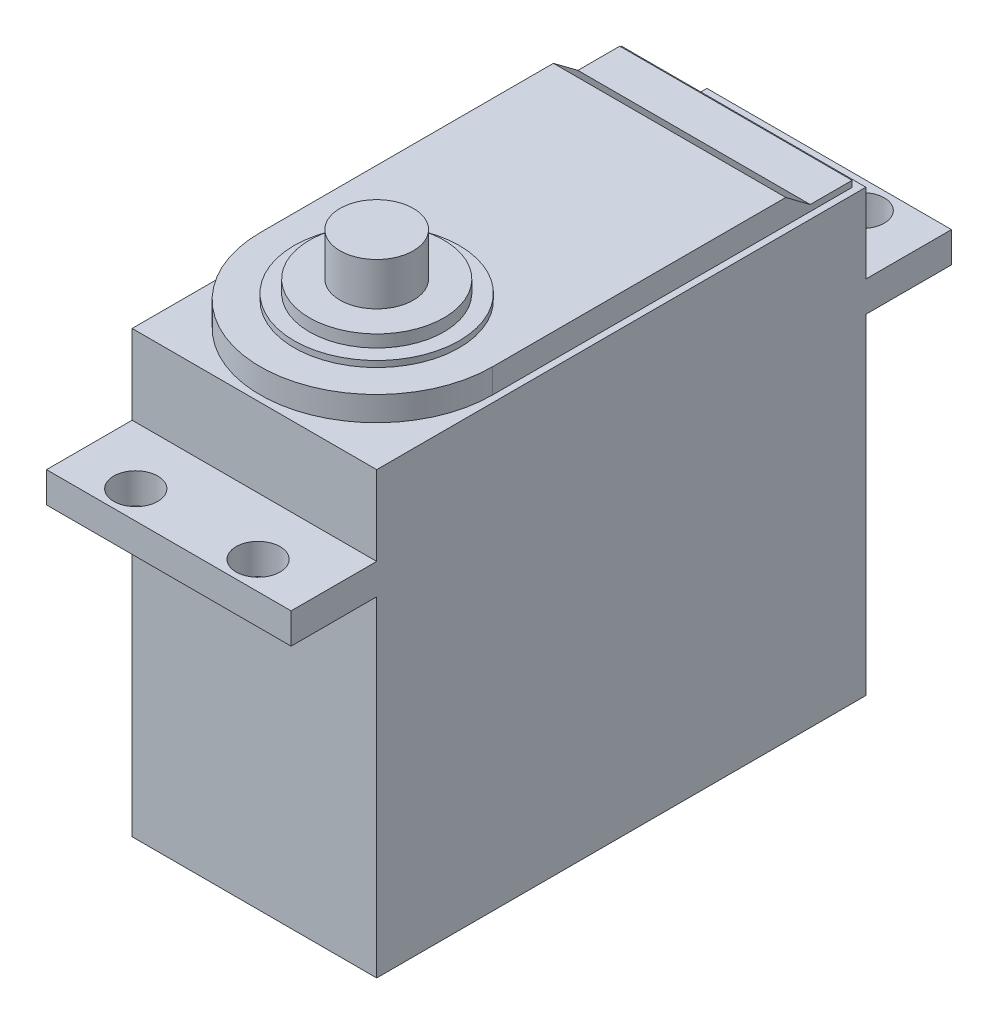
SolidWorks part; units mm, degrees
ref_plane "Front Plane" through (0, 0, 0) normal (0, 0, 1) x (1, 0, 0)
ref_plane "Top Plane" through (0, 0, 0) normal (0, 1, 0) x (1, 0, 0)
ref_plane "Right Plane" through (0, 0, 0) normal (1, 0, 0) x (0, 0, -1)
sketch "Sketch1" plane through (0, 0, 0) normal (0, 0, 1) x (1, 0, 0)
  line L1 (0, 0) -> (20, 0)
  line L2 (0, 0) -> (0, 38)
  line L3 (0, 38) -> (20, 38)
  line L4 (20, 0) -> (20, 38)
  dimension "D1" = 20
  dimension "D2" = 38
extrude "Boss-Extrude1" add sketch "Sketch1" along normal blind 40
sketch "Sketch2" plane through (0, 0, 0) normal (-1, 0, 0) x (0, 0, 1)
  line L0 (0, 0) -> (0, 38) construction
  line L1 (0, 29.5) -> (-7, 29.5)
  line L2 (0, 29.5) -> (0, 27)
  line L3 (0, 27) -> (-7, 27)
  line L4 (-7, 29.5) -> (-7, 27)
  line L5 (40, 0) -> (0, 0) construction
  line L6 (40, 0) -> (40, 38) construction
  line L7 (40, 29.5) -> (47, 29.5)
  line L8 (40, 29.5) -> (40, 27)
  line L9 (40, 27) -> (47, 27)
  line L10 (47, 29.5) -> (47, 27)
  dimension "D1" = 29.5
  dimension "D2" = 2.5
  dimension "D3" = 7
  dimension "D4" = 7
  dimension "D5" = 29.5
  dimension "D6" = 2.5
extrude "Boss-Extrude2" add sketch "Sketch2" against normal up to surface (20 mm away) up to face at (20, 19, 20)
sketch "Sketch3" plane through (0, 0, 0) normal (-1, 0, 0) x (0, 0, 1)
  line L0 (6, 38) -> (4, 36.5)
  line L1 (40, 38) -> (0, 38) construction
  line L2 (4, 36.5) -> (0, 36.5)
  line L3 (0, 29.5) -> (0, 38) construction
  line L4 (6, 38) -> (0, 38)
  line L5 (0, 38) -> (0, 36.5)
  dimension "D1" = 1.5
  dimension "D2" = 4
  dimension "D3" = 6
extrude "Cut-Extrude1" cut sketch "Sketch3" against normal blind 40
sketch "Sketch4" plane through (0, 29.5, 0) normal (0, 1, 0) x (1, 0, 0)
  line L0 (20, -40) -> (0, -40) construction
  line L1 (0, -47) -> (0, -40) construction
  line L2 (0, 0) -> (0, 7) construction
  line L3 (20, 0) -> (0, 0) construction
  circle A0 centre (15, -44.7) radius 1.8
  circle A1 centre (5, -44.7) radius 1.8
  circle A3 centre (15, 4.7) radius 1.8
  circle A4 centre (5, 4.7) radius 1.8
  dimension "D1" = 3.6
  dimension "D2" = 10
  dimension "D3" = 4.7
  dimension "D4" = 4.7
  dimension "D5" = 5
  dimension "D6" = 10
  dimension "D7" = 5
  dimension "D8" = 4.7
extrude "Cut-Extrude2" cut sketch "Sketch4" against normal blind 10
sketch "Sketch5" plane through (0, 38, 0) normal (0, 1, 0) x (1, 0, 0)
  line L0 (19.4497, -29.976) -> (19.4497, -0.5757)
  line L1 (0.4497, -29.976) -> (0.4497, -0.5757)
  line L2 (0.4497, -0.5757) -> (19.4497, -0.5757)
  line L3 (20, -40) -> (0, -40)
  line L4 (0, -40) -> (0, 0)
  line L5 (0, 0) -> (20, 0)
  line L6 (20, 0) -> (20, -40)
  arc A0 (0.4497, -29.976) -> (19.4497, -29.976) centre (9.9497, -29.976) ccw
extrude "Cut-Extrude3" cut sketch "Sketch5" against normal blind 2
sketch "Sketch6" plane through (0, 38, 0) normal (0, 1, 0) x (1, 0, 0)
  line L0 (20, -40) -> (20, 0) construction
  line L2 (20, -40) -> (0, -40) construction
  circle A0 centre (10, -30) radius 6.75
  circle A1 centre (10, -30) radius 5.5
  circle A2 centre (10, -30) radius 3
  dimension "D3" = 13.5
  dimension "D4" = 11
  dimension "D5" = 6
  dimension "D1" = 10
  dimension "D2" = 10
extrude "Boss-Extrude3" add sketch "Sketch6" along normal blind 0.5 contours A0 A1 region at (3.4409, 38, 30)
extrude "Boss-Extrude4" add sketch "Sketch6<4>" along normal blind 1.5 contours A1 A2 region at (4.6556, 38, 30)
sketch "Sketch6<4>" plane through (0, 38, 0) normal (0, 1, 0) x (1, 0, 0) same geometry as "Sketch6"
extrude "Boss-Extrude5" add sketch "Sketch6<5>" along normal blind 5 contours A2 region at (10, 38, 30)
sketch "Sketch6<5>" plane through (0, 38, 0) normal (0, 1, 0) x (1, 0, 0) same geometry as "Sketch6"
